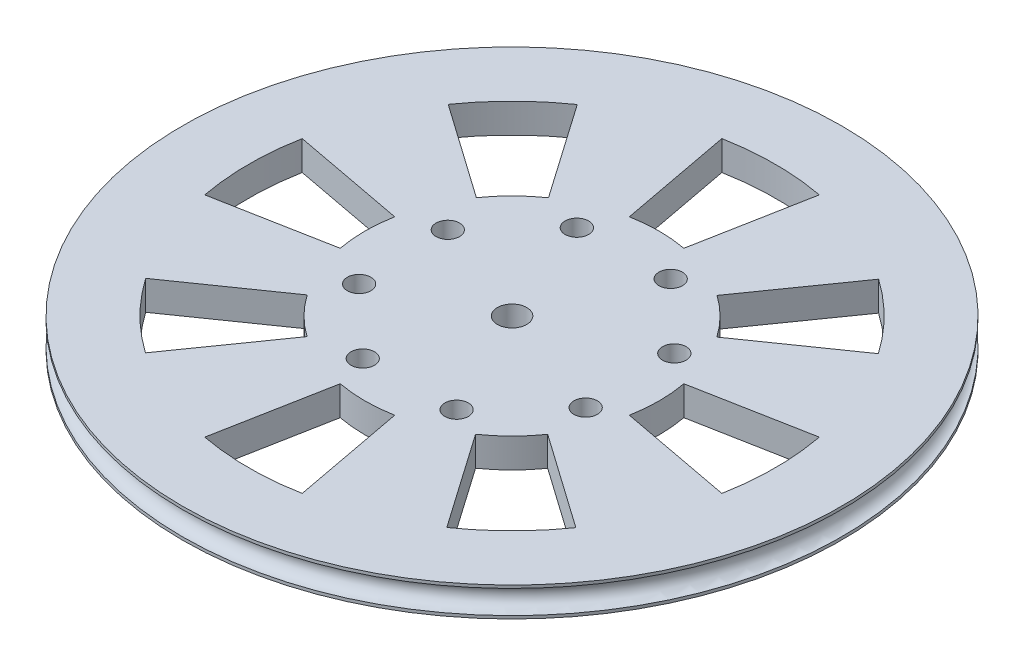
SolidWorks part; units mm, degrees
ref_plane "Front Plane" through (0, 0, 0) normal (0, 0, 1) x (1, 0, 0)
ref_plane "Top Plane" through (0, 0, 0) normal (0, 1, 0) x (1, 0, 0)
ref_plane "Right Plane" through (0, 0, 0) normal (1, 0, 0) x (0, 0, -1)
sketch "Sketch6" plane through (0, 0, 0) normal (0, 1, 0) x (1, 0, 0)
  circle A0 centre (0, 0) radius 56
  dimension "D1" = 112
extrude "Boss-Extrude3" add sketch "Sketch6" along normal blind 5
sketch "Sketch7" plane through (0, 5, 0) normal (0, 1, 0) x (1, 0, 0)
  line L0 (43.9376, 8.2828) -> (21.2987, 8.2828)
  line L1 (0, 0) -> (36.6693, 25.5828)
  line L2 (-43.9376, -8.2828) -> (-19.7033, -8.2828)
  line L3 (0, 0) -> (25.7254, 36.5694)
  line L4 (-36.6693, -25.5828) -> (-19.6695, -8.649)
  line L5 (0, 0) -> (8.2828, 43.9376)
  line L6 (-8.2828, 43.9376) -> (-8.2828, 20.335)
  line L7 (0, 0) -> (-8.2828, 43.9376)
  line L8 (8.2828, 43.9376) -> (8.2828, 20.922)
  line L9 (0, 0) -> (-25.5828, 36.6693)
  line L10 (36.6693, 25.5828) -> (20.7172, 9.6927)
  line L11 (0, 0) -> (-36.5694, 25.7254)
  line L12 (0, 0) -> (-43.9376, 8.2828)
  line L13 (0, 0) -> (-43.9376, -8.2828)
  line L14 (-25.5828, 36.6693) -> (-8.8965, 19.9179)
  line L15 (0, 0) -> (-36.6693, -25.5828)
  line L16 (25.5828, -36.6693) -> (9.4441, -20.4676)
  line L17 (0, 0) -> (-25.7254, -36.5694)
  line L18 (0, 0) -> (-8.2828, -43.9376)
  line L19 (0, 0) -> (8.2828, -43.9376)
  line L20 (0, 0) -> (25.5828, -36.6693)
  line L21 (0, 0) -> (36.5694, -25.7254)
  line L22 (0, 0) -> (43.9376, -8.2828)
  line L23 (0, 0) -> (43.9376, 8.2828)
  line L24 (0.7977, 0) -> (9.5683, 21.1742) construction
  line L25 (-8.2828, 16.667) -> (-8.2828, -18.1916)
  line L26 (-6.0736, 17.084) -> (17.7714, -6.8541)
  line L27 (8.2828, 16.9559) -> (8.2828, -16.667)
  line L28 (9.4416, 20.3489) -> (25.7254, 36.5694)
  line L29 (17.8833, 6.8698) -> (-6.0538, -16.9742)
  line L30 (17.2987, 8.2828) -> (-16.4437, 8.2828)
  line L31 (21.4343, -8.2828) -> (43.9376, -8.2828)
  line L32 (20.1003, -9.192) -> (36.5694, -25.7254)
  line L33 (7.1152, -18.1297) -> (-16.7298, 5.8084)
  line L34 (8.2828, -20.335) -> (8.2828, -43.9376)
  line L35 (-8.2828, -19.6863) -> (-8.2828, -43.9376)
  line L36 (-8.3938, -19.3052) -> (-25.7254, -36.5694)
  line L37 (-17.3294, -6.318) -> (6.6076, 17.526)
  line L38 (-15.7033, -8.2828) -> (18.0391, -8.2828)
  line L39 (-19.8389, 8.2828) -> (-43.9376, 8.2828)
  line L40 (-19.5527, 8.6423) -> (-36.5694, 25.7254)
  circle A0 centre (0, 0) radius 44.7115
  circle A1 centre (0, 0) radius 25
  arc A2 (-9.2743, 17.6073) -> (-17.6632, 9.1674) centre (0, 0) ccw
  circle A3 centre (8.0231, 18.939) radius 2
  circle A4 centre (19.2987, 8.2828) radius 2
  circle A5 centre (19.7367, -7.2254) radius 2
  circle A6 centre (9.0805, -18.501) radius 2
  circle A7 centre (-6.4277, -18.939) radius 2
  circle A8 centre (-17.7033, -8.2828) radius 2
  circle A9 centre (-18.1413, 7.2254) radius 2
  circle A10 centre (-7.4851, 18.501) radius 2
  arc A11 (6.0233, 18.9671) -> (-5.5778, 19.1028) centre (0, 0) ccw
  arc A12 (17.5857, 9.3151) -> (9.4345, 17.522) centre (0, 0) ccw
  arc A13 (19.1806, -5.3042) -> (18.8669, 6.3299) centre (0, 0) ccw
  arc A14 (10.3788, -16.9797) -> (18.0716, -8.3334) centre (0, 0) ccw
  arc A15 (-4.4791, -19.3899) -> (7.0828, -18.5974) centre (0, 0) ccw
  arc A16 (-17.0949, -10.188) -> (-8.2481, -18.1107) centre (0, 0) ccw
  arc A17 (-19.1293, 5.4864) -> (-18.776, -6.5948) centre (0, 0) ccw
  dimension "D1" = 20
  dimension "D2" = 8
  dimension "D3" = 4
extrude "Cut-Extrude4" cut sketch "Sketch7" against normal through all both and the other way through all contours A1 L1 A0 L3 | A1 L5 A0 L7 | A1 L9 A0 L11 | A1 L12 A0 L13 | A1 L15 A0 L17 | A1 L18 A0 L19 | A1 L20 A0 L21 | A1 L22 A0 L23 region at (35.578, 5, 0) region at (25.2246, 5, -25.1266) region at (25.1266, 5, 25.2246) region at (0, 5, -35.578) region at (0, 5, 35.578) region at (-25.1266, 5, -25.2246) region at (-25.2246, 5, 25.1266) region at (-35.578, 5, 0)
extrude "Cut-Extrude5" cut sketch "Sketch7<8>" against normal through all both and the other way through all contours A10 | A4 | A5 | A6 | A7 | A8 | A9 | L24 A3 | A3 L24 region at (19.2987, 5, -8.2828) region at (19.7367, 5, 7.2254) region at (9.0998, 5, -18.493) region at (7.5155, 5, -19.1492) region at (9.0805, 5, 18.501) region at (-7.4851, 5, -18.501) region at (-6.4277, 5, 18.939) region at (-18.1413, 5, -7.2254) region at (-17.7033, 5, 8.2828)
sketch "Sketch7<8>" plane through (0, 5, 0) normal (0, 1, 0) x (1, 0, 0) same geometry as "Sketch7"
sketch "Sketch10" plane through (0, 0, 0) normal (0, 0, 1) x (1, 0, 0)
  line L0 (56, 0) -> (56, 5) construction
  circle A0 centre (56, 2.5) radius 2
  dimension "D1" = 4
ref_axis "Axis1" through (0, 40.6143, 0) along (0, -1, 0)
revolve "Cut-Revolve1" cut sketch "Sketch10" angle 360 about axis through (0, 40.6143, 0) along (0, -1, 0)
sketch "Sketch11" plane through (0, 0, 0) normal (0, 1, 0) x (1, 0, 0)
  circle A0 centre (0, 0) radius 2.5
  dimension "D1" = 5
extrude "Cut-Extrude14" cut sketch "Sketch11" against normal blind 5 and the other way through all
sketch "Sketch12" plane through (0, 0, 0) normal (0, 1, 0) x (1, 0, 0)
  line L1 (0, 7) -> (-6.0622, 3.5)
  line L2 (-6.0622, 3.5) -> (-6.0622, -3.5)
  line L3 (-6.0622, -3.5) -> (0, -7)
  line L4 (0, -7) -> (6.0622, -3.5)
  line L5 (6.0622, -3.5) -> (6.0622, 3.5)
  line L6 (6.0622, 3.5) -> (0, 7)
  circle A0 centre (0, 0) radius 9
  circle A1 centre (0, 0) radius 6.0622 construction
  dimension "D2" = 18
  dimension "D1" = 7
extrude "Boss-Extrude4" add sketch "Sketch12" against normal blind 4
